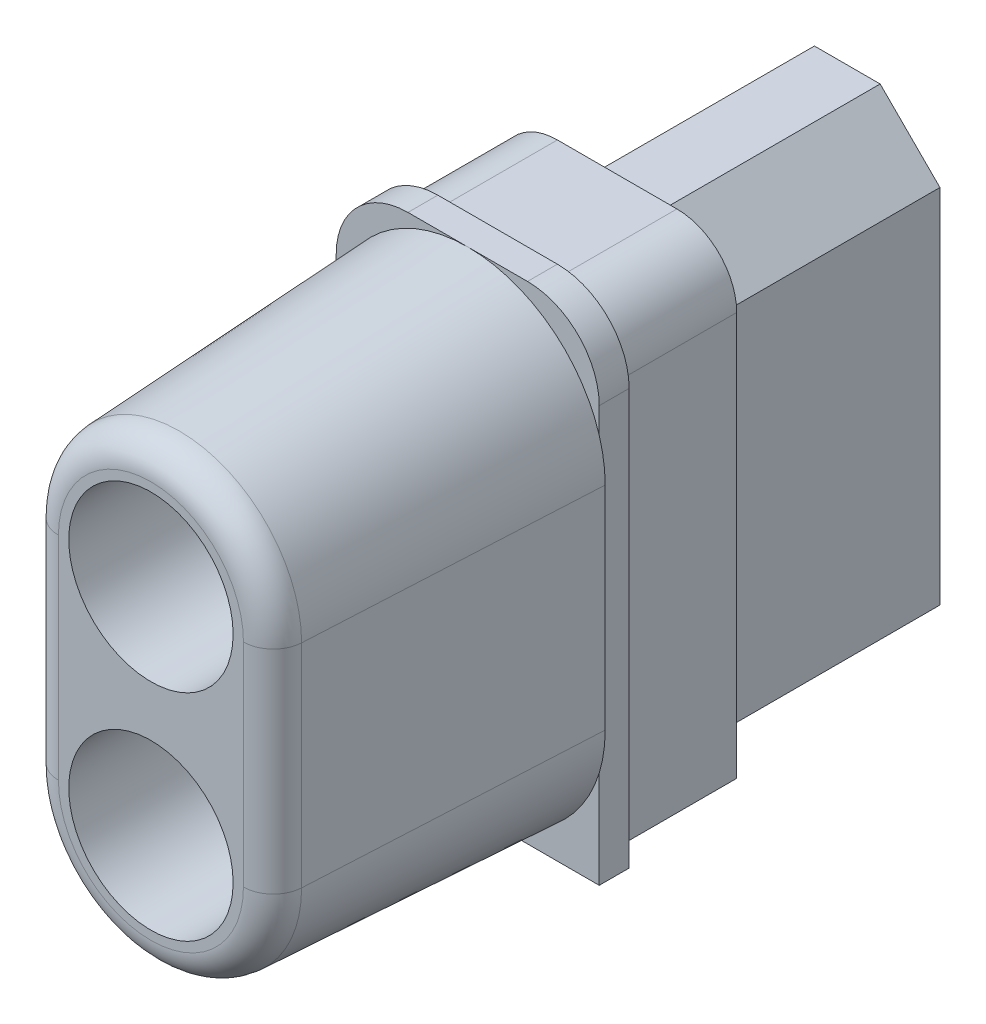
SolidWorks part; units mm, degrees
material "PEI"
ref_plane "前视基准面" through (0, 0, 0) normal (0, 0, 1) x (1, 0, 0)
ref_plane "上视基准面" through (0, 0, 0) normal (0, 1, 0) x (1, 0, 0)
ref_plane "右视基准面" through (0, 0, 0) normal (1, 0, 0) x (0, 0, -1)
other "Configuration Table"
sketch "草图1" plane through (0, 0, 0) normal (0, 0, 1) x (1, 0, 0)
  line L0 (0, 12.1) -> (2, 14.1)
  line L1 (0, 0) -> (6.2, 0)
  line L2 (0, 0) -> (0, 12.1)
  line L3 (2, 14.1) -> (4.2, 14.1)
  line L4 (6.2, 0) -> (6.2, 12.1)
  line L5 (4.2, 14.1) -> (6.2, 12.1)
  line L6 (0, 7.05) -> (6.2, 7.05) construction
  circle A0 centre (3.1, 3.45) radius 1.6
  circle A1 centre (3.1, 10.65) radius 1.6
  point P1 (6.2, 14.1)
  point P2 (0, 14.1)
  point P11 (3.1, 0)
  dimension "D3" = 3.2
  dimension "D1" = 6.2
  dimension "D2" = 14.1
  dimension "D4" = 7.2
  dimension "D5" = 7.05
extrude "凸台-拉伸1" add sketch "草图1" along normal blind 7.7
sketch "草图2" plane through (0, 0, 7.7) normal (0, 0, 1) x (1, 0, 0)
  line L1 (1.1, 14.778) -> (5.1, 14.778)
  line L2 (-0.9, 12.778) -> (-0.9, -0.722)
  line L3 (-0.9, -0.722) -> (7.1, -0.722)
  line L4 (7.1, 12.778) -> (7.1, -0.722)
  line L5 (3.1, 14.1) -> (3.1, 0) construction
  line L6 (4.2, 14.1) -> (2, 14.1) construction
  line L7 (0, 0) -> (6.2, 0) construction
  line L8 (0, 7.028) -> (6.2, 7.028) construction
  line L9 (0, 12.1) -> (0, 0) construction
  line L10 (6.2, 0) -> (6.2, 12.1) construction
  arc A0 (5.1, 14.778) -> (7.1, 12.778) centre (5.1, 12.778) cw
  arc A1 (1.1, 14.778) -> (-0.9, 12.778) centre (1.1, 12.778) ccw
  point P18 (7.1, 14.778)
  point P21 (-0.9, 14.778)
  dimension "D3" = 2
  dimension "D1" = 15.5
  dimension "D2" = 8
extrude "凸台-拉伸2" add sketch "草图2" along normal blind 4
sketch "草图3" plane through (0, 0, 11.7) normal (0, 0, 1) x (1, 0, 0)
  line L0 (-1.3, 12.778) -> (-1.3, -1.122)
  line L1 (-1.3, -1.122) -> (7.5, -1.122)
  line L2 (7.5, -1.122) -> (7.5, 12.778)
  line L3 (5.1, 15.178) -> (1.1, 15.178)
  line L4 (7.1, -0.722) -> (7.1, 12.778)
  line L5 (5.1, 14.778) -> (1.1, 14.778)
  line L6 (-0.9, 12.778) -> (-0.9, -0.722)
  line L7 (-0.9, -0.722) -> (7.1, -0.722)
  line L8 (7.1, -0.722) -> (7.1, 12.778)
  line L9 (5.1, 14.778) -> (1.1, 14.778)
  line L10 (-0.9, 12.778) -> (-0.9, -0.722)
  line L11 (-0.9, -0.722) -> (7.1, -0.722)
  arc A0 (7.5, 12.778) -> (5.1, 15.178) centre (5.1, 12.778) ccw
  arc A1 (1.1, 15.178) -> (-1.3, 12.778) centre (1.1, 12.778) ccw
  arc A2 (7.1, 12.778) -> (5.1, 14.778) centre (5.1, 12.778) ccw
  arc A3 (1.1, 14.778) -> (-0.9, 12.778) centre (1.1, 12.778) ccw
  arc A4 (7.1, 12.778) -> (5.1, 14.778) centre (5.1, 12.778) ccw
  arc A5 (1.1, 14.778) -> (-0.9, 12.778) centre (1.1, 12.778) ccw
  line M7 (7.1, -0.722) -> (7.1, 12.778)
  arc M8 (7.1, 12.778) -> (5.1, 14.778) centre (5.1, 12.778) ccw
  line M9 (5.1, 14.778) -> (1.1, 14.778)
  arc M10 (1.1, 14.778) -> (-0.9, 12.778) centre (1.1, 12.778) ccw
  line M11 (-0.9, 12.778) -> (-0.9, -0.722)
  line M12 (-0.9, -0.722) -> (7.1, -0.722)
  dimension "D1" = 0
  dimension "D2" = 0.4
extrude "凸台-拉伸3" add sketch "草图3" along normal blind 1 contours M12 M7 M8 M9 M10 M11 | L3 A1 L0 L1 L2 A0 M7 M12 M11 M10 M9 M8 region at (-0.4661, 14.344, 11.7) region at (3.1, 6.9254, 11.7)
sketch "草图4" plane through (0, 0, 12.7) normal (0, 0, 1) x (1, 0, 0)
  line L0 (3.1, 15.178) -> (3.1, -1.122) construction
  line L1 (5.1, 15.178) -> (1.1, 15.178) construction
  line L2 (-1.3, -1.122) -> (7.5, -1.122) construction
  line L3 (-1.3, 7.028) -> (7.5, 7.028) construction
  line L4 (-1.3, 12.778) -> (-1.3, -1.122) construction
  line L5 (7.5, -1.122) -> (7.5, 12.778) construction
  line L6 (3.1, 10.578) -> (3.1, 3.478) construction
  line L7 (7.7, 10.578) -> (7.7, 3.478)
  line L8 (-1.5, 10.578) -> (-1.5, 3.478)
  arc A0 (7.7, 10.578) -> (-1.5, 10.578) centre (3.1, 10.578) ccw
  arc A1 (-1.5, 3.478) -> (7.7, 3.478) centre (3.1, 3.478) ccw
  circle A2 centre (3.1, 10.628) radius 2.75
  circle A3 centre (3.1, 3.428) radius 2.75
  point P14 (3.1, 7.028)
  dimension "D2" = 5.5
  dimension "D3" = 5.5
  dimension "D1" = 9.2
  dimension "D4" = 7.2
extrude "凸台-拉伸4" add sketch "草图4" along normal blind 10.6
draft "拔模2" type of draft neutral plane draft angle 3 faces to draft 4 face at (3.1, 1.5708, 15.7286) face at (3.1, 12.4851, 15.7286) face at (-1.5, 7.028, 18) face at (7.7, 7.028, 18) neutral plane through (0, 0, 12.7) neutral plane normal (0, 0, 1) parameters "D1"=3
fillet "圆角1" radius 1 4 edges at (3.1, 14.6225, 23.3) (7.1445, 7.028, 23.3) (3.1, -0.5665, 23.3) (-0.9445, 7.028, 23.3)
other "连接点1" parameters "直径"=5, "端头长度"=3
ref_axis "基准轴1" through (3.1, 10.628, 33.3) along (0, 0, -1)
other "连接点2" parameters "直径"=5, "端头长度"=3
ref_axis "基准轴2" through (3.1, 3.428, 33.3) along (0, 0, -1)
